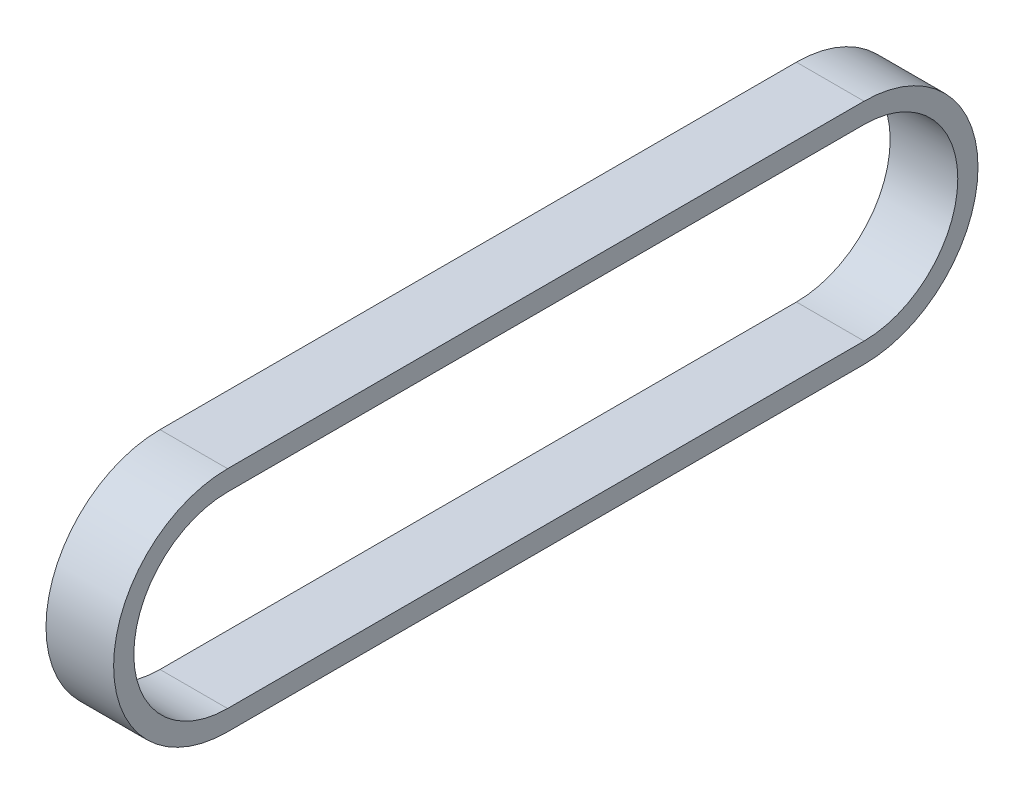
SolidWorks part; units mm, degrees
ref_plane "Front" through (0, 0, 0) normal (0, 0, 1) x (1, 0, 0)
ref_plane "Top" through (0, 0, 0) normal (0, 1, 0) x (1, 0, 0)
ref_plane "Right" through (0, 0, 0) normal (1, 0, 0) x (0, 0, -1)
sketch "Sketch1" plane through (0, 0, 0) normal (1, 0, 0) x (0, 0, -1)
  line L0 (-40.005, 0) -> (40.005, 0) construction
  line L1 (-40.005, 14.3256) -> (40.005, 14.3256)
  line L2 (-40.005, -14.3256) -> (40.005, -14.3256)
  arc A0 (-40.005, 14.3256) -> (-40.005, -14.3256) centre (-40.005, 0) ccw
  arc A1 (40.005, -14.3256) -> (40.005, 14.3256) centre (40.005, 0) ccw
  point P2 (0, 0)
  dimension "D2" = 28.6512
  dimension "D1" = 80.01
extrude "Extrude-Thin1" add sketch "Sketch1" along normal blind 8.5 thin thin type one direction reverse wall 2.54
